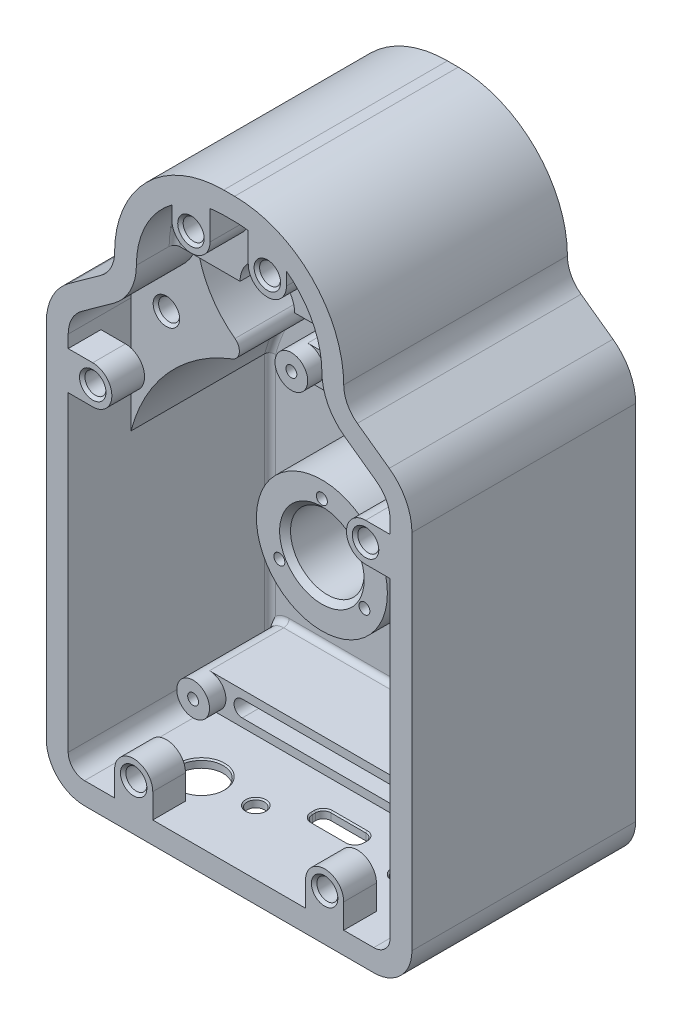
SolidWorks part; units mm, degrees
ref_plane "Plano frontal" through (0, 0, 0) normal (0, 0, 1) x (1, 0, 0)
ref_plane "Plano superior" through (0, 0, 0) normal (0, 1, 0) x (1, 0, 0)
ref_plane "Plano direito" through (0, 0, 0) normal (1, 0, 0) x (0, 0, -1)
sketch "Esboço1" plane through (0, 0, 0) normal (0, 0, 1) x (1, 0, 0)
  line L0 (-33.5, 0) -> (33.5, 0) construction
  line L1 (-33.5, -44.5) -> (33.5, -44.5)
  line L2 (-33.5, -44.5) -> (-33.5, 66)
  line L3 (-33.5, 66) -> (33.5, 66)
  line L4 (33.5, -44.5) -> (33.5, 66)
  point P0 (0, 0)
  point P8 (0, 0)
  dimension "D1" = 67
  dimension "D2" = 66
  dimension "D3" = 44.5
  dimension "D4" = 0
extrude "Ressalto-extrusão1" add sketch "Esboço1" along normal blind 4
sketch "Esboço2" plane through (0, 0, 4) normal (0, 0, 1) x (1, 0, 0)
  circle A0 centre (0, 0) radius 12
  dimension "D1" = 24
extrude "Ressalto-extrusão2" add sketch "Esboço2" along normal blind 20
sketch "Esboço3" plane through (0, 0, 24) normal (0, 0, 1) x (1, 0, 0)
  circle A0 centre (0, 9) radius 1
  circle A1 centre (7.7942, -4.5) radius 1
  circle A2 centre (-7.7942, -4.5) radius 1
  point P10 (0, 0)
  dimension "D1" = 9
  dimension "D2" = 2
  dimension "D3" = 3
extrude "Corte-extrusão1" cut sketch "Esboço3" against normal blind 6
sketch "Esboço4" plane through (0, 0, 4) normal (0, 0, 1) x (1, 0, 0)
  line L1 (5, -12.5) -> (-5, -12.5)
  line L2 (5, -12.5) -> (5, 12.5)
  line L3 (5, 12.5) -> (-5, 12.5)
  line L4 (-5, -12.5) -> (-5, 12.5)
  line L5 (5, -12.5) -> (-5, 12.5) construction
  line L6 (5, 12.5) -> (-5, -12.5) construction
  point P0 (0, 0)
  dimension "D1" = 10
  dimension "D2" = 25
extrude "Corte-extrusão2" cut sketch "Esboço4" along normal blind 8
sketch "Esboço5" plane through (0, 0, 24) normal (0, 0, 1) x (1, 0, 0)
  circle A0 centre (0, 0) radius 6.75
  dimension "D1" = 13.5
extrude "Corte-extrusão3" cut sketch "Esboço5" against normal up to surface (20 mm away) up to face at (-8.5, 0, 4)
sketch "Esboço6" plane through (0, 0, 4) normal (0, 0, 1) x (1, 0, 0)
  line L0 (0, 66) -> (0, -44.5) construction
  line L1 (33.5, 66) -> (-33.5, 66) construction
  line L2 (-33.5, -44.5) -> (33.5, -44.5) construction
  line L4 (26, -40) -> (-26, -40)
  line L6 (26, -34) -> (-26, -34)
  line L8 (-8, 27) -> (8, 27)
  line L9 (-8, 21) -> (8, 21)
  circle A0 centre (-26, -37) radius 1
  circle A1 centre (26, -37) radius 1
  arc A2 (-26, -34) -> (-26, -40) centre (-26, -37) ccw
  arc A3 (26, -34) -> (26, -40) centre (26, -37) cw
  circle A4 centre (-8, 24) radius 1
  arc A5 (-8, 27) -> (-8, 21) centre (-8, 24) ccw
  arc A6 (8, 27) -> (8, 21) centre (8, 24) cw
  circle A7 centre (8, 24) radius 1
  point P11 (0, -40)
  point P17 (0, -34)
  point P23 (0, 27)
  point P27 (0, 21)
  dimension "D1" = 26
  dimension "D2" = 37
  dimension "D3" = 2
  dimension "D5" = 2
  dimension "D7" = 24
  dimension "D8" = 8
  dimension "D9" = 6
  dimension "D4" = 3
  dimension "D6" = 3
extrude "Ressalto-extrusão3" add sketch "Esboço6" along normal blind 14.6
sketch "Esboço7" plane through (0, 0, 18.6) normal (0, 0, 1) x (1, 0, 0)
  line L0 (0, -34) -> (0, -40) construction
  line L1 (26, -34) -> (-26, -34) construction
  line L2 (-26, -40) -> (26, -40) construction
  circle A0 centre (-26, -37) radius 1
  circle A1 centre (-26, -37) radius 3
  circle A2 centre (26, -37) radius 3
  circle A3 centre (26, -37) radius 1
  circle A4 centre (-8, 24) radius 1
  circle A5 centre (-8, 24) radius 3
  circle A6 centre (8, 24) radius 1
  circle A7 centre (8, 24) radius 3
extrude "Ressalto-extrusão4" add sketch "Esboço7" along normal blind 3
sketch "Esboço12" plane through (0, 0, 4) normal (0, 0, 1) x (1, 0, 0)
  line L0 (0, 66) -> (0, -44.5) construction
  line L1 (-33.5, 66) -> (-21, 66)
  line L2 (-33.5, 66) -> (-33.5, 34)
  line L4 (-21, 66) -> (-21, 43)
  line L5 (33.5, 66) -> (-33.5, 66) construction
  line L6 (-33.5, -44.5) -> (33.5, -44.5) construction
  line L9 (33.5, 66) -> (33.5, 34)
  line L10 (33.5, 66) -> (21, 66)
  line L11 (-33.5, 34) -> (-21, 43)
  line L12 (33.5, 34) -> (21, 43)
  line L13 (21, 66) -> (21, 43)
  dimension "D1" = 32
  dimension "D2" = 23
  dimension "D3" = 12.5
extrude "Corte-extrusão4" cut sketch "Esboço12" against normal through all
sketch "Esboço10" plane through (0, 0, 4) normal (0, 0, 1) x (1, 0, 0)
  line L24 (-33.5, 34) -> (-21, 43)
  line L25 (-21, 43) -> (-21, 66)
  line L26 (-21, 66) -> (21, 66)
  line L27 (21, 66) -> (21, 43)
  line L28 (21, 43) -> (33.5, 34)
  line L29 (33.5, 34) -> (33.5, -44.5)
  line L30 (33.5, -44.5) -> (-33.5, -44.5)
  line L31 (-33.5, -44.5) -> (-33.5, 34)
  line L32 (-29.5, 31.9511) -> (-17, 40.9511)
  line L33 (-17, 40.9511) -> (-17, 62)
  line L34 (-17, 62) -> (17, 62)
  line L35 (17, 62) -> (17, 40.9511)
  line L36 (17, 40.9511) -> (29.5, 31.9511)
  line L37 (29.5, 31.9511) -> (29.5, -40.5)
  line L38 (29.5, -40.5) -> (-29.5, -40.5)
  line L39 (-29.5, -40.5) -> (-29.5, 31.9511)
  dimension "D1" = 4
extrude "Ressalto-extrusão5" add sketch "Esboço10" along normal blind 37
fillet "Filete5" radius 7 2 edges at (33.5, -44.5, 20.5) (-33.5, -44.5, 20.5)
fillet "Filete12" radius 3 2 edges at (29.5, -40.5, 22.5) (-29.5, -40.5, 22.5)
fillet "Filete13" radius 6 4 edges at (29.5, 31.9511, 22.5) (21, 43, 20.5) (-21, 43, 20.5) (-29.5, 31.9511, 22.5)
fillet "Filete14" radius 10 4 edges at (-33.5, 34, 20.5) (-17, 40.9511, 22.5) (33.5, 34, 20.5) (17, 40.9511, 22.5)
fillet "Filete15" radius 16 2 edges at (17, 62, 22.5) (-17, 62, 22.5)
fillet "Filete16" radius 20 2 edges at (21, 66, 20.5) (-21, 66, 20.5)
sketch "Esboço13" plane through (0, 0, 4) normal (0, 0, 1) x (1, 0, 0)
  line L0 (1.0001, 62) -> (-1.0001, 62) construction
  line L1 (-5, 46) -> (-17.0001, 46)
  line L2 (5, 46) -> (17.0001, 46)
  line L3 (-1.0001, 62) -> (1.0001, 62)
  arc A0 (-1.0001, 62) -> (-17.0001, 46) centre (-1.0001, 46) ccw
  arc A1 (17.0001, 46) -> (1.0001, 62) centre (1.0001, 46) ccw
  arc A2 (5, 46) -> (-5, 46) centre (0, 46) ccw
  dimension "D1" = 16
  dimension "D2" = 10
extrude "Ressalto-extrusão6" add sketch "Esboço13" along normal blind 4 from offset 26
sketch "Esboço14" plane through (0, 0, 34) normal (0, 0, 1) x (1, 0, 0)
  circle A0 centre (0, 58) radius 1.3
  circle A1 centre (10.3923, 52) radius 1.3
  circle A2 centre (10.3923, 40) radius 1.3
  circle A3 centre (0, 34) radius 1.3
  circle A4 centre (-10.3923, 40) radius 1.3
  circle A5 centre (-10.3923, 52) radius 1.3
  arc A6 (5, 46) -> (-5, 46) centre (0, 46) ccw construction
  point P15 (0, 46)
  dimension "D1" = 2.6
  dimension "D3" = 12
  dimension "D2" = 6
extrude "Corte-extrusão5" cut sketch "Esboço14" against normal blind 4
fillet "Filete17" radius 1 3 edges at (-12.2978, 57.3297, 34) (0, 62, 34) (12.2978, 57.3297, 34)
sketch "Esboço20" plane through (0, 0, 4) normal (0, 0, 1) x (1, 0, 0)
  line L4 (-29.5, 7.746) -> (-29.5, 28.8777)
  line L5 (-27.0058, 33.7469) -> (-21.157, 37.9581)
  arc A1 (-21.157, 37.9581) -> (-17.3262, 43.54) centre (-27, 46.0734) ccw
  arc A2 (-27.0058, 33.7469) -> (-29.5, 28.8777) centre (-23.5, 28.8777) ccw
  arc A3 (-6.5762, 29.7826) -> (-29.5, 7.746) centre (0, 0) ccw
  arc A4 (-17.3262, 43.54) -> (-6.5762, 29.7826) centre (0, 46) ccw
  dimension "D4" = 61
  dimension "D1" = 35
extrude "Ressalto-extrusão9" add sketch "Esboço20" along normal blind 25.5
fillet "Filete18" radius 2 1 edges at (-6.5762, 29.7826, 16.75)
sketch "Esboço21" plane through (0, 0, 29.5) normal (0, 0, 1) x (1, 0, 0)
  circle A0 centre (-23, 30) radius 1.925
  dimension "D1" = 30
  dimension "D2" = 23
  dimension "D3" = 3.85
extrude "Corte-extrusão6" cut sketch "Esboço21" against normal blind 6.5
sketch "Esboço22" plane through (0, 0, 4) normal (0, 0, 1) x (1, 0, 0)
  line L0 (0, 0) -> (0, -44.5) construction
  line L1 (-26.5, -44.5) -> (26.5, -44.5) construction
  line L2 (0, 0) -> (33.5, 0) construction
  line L3 (33.5, -37.5) -> (33.5, 28.8777) construction
  circle A0 centre (-18, -25) radius 4
  circle A1 centre (18, -25) radius 4
  circle A2 centre (18, 25) radius 4
  circle A3 centre (-18, 25) radius 4
  circle A4 centre (0, 53) radius 4
  arc A5 (5, 46) -> (-5, 46) centre (0, 46) ccw construction
  dimension "D1" = 8
  dimension "D2" = 18
  dimension "D3" = 25
  dimension "D4" = 8
  dimension "D5" = 7
extrude "Ressalto-extrusão10" add sketch "Esboço22" along normal blind 2
sketch "Esboço23" plane through (0, 0, 6) normal (0, 0, 1) x (1, 0, 0)
  circle A0 centre (0, 53) radius 1.925
  circle A1 centre (-18, 25) radius 1.925
  circle A2 centre (18, 25) radius 1.925
  circle A3 centre (-18, -25) radius 1.925
  circle A4 centre (18, -25) radius 1.925
  dimension "D1" = 3.85
  dimension "D2" = 3.85
  dimension "D3" = 3.85
  dimension "D4" = 3.85
  dimension "D5" = 3.85
extrude "Corte-extrusão7" cut sketch "Esboço23" against normal through all from offset 1.5 offset against normal yes
sketch "Esboço24" plane through (0, 0, 41) normal (0, 0, 1) x (1, 0, 0)
  line L0 (-10.5, 56.5) -> (-10.5, 58.8745)
  line L1 (-3.5, 56.5) -> (-3.5, 61.8035)
  line L2 (0, 46) -> (0, 62) construction
  line L3 (1.0001, 62) -> (-1.0001, 62) construction
  line L4 (3.5, 56.5) -> (3.5, 61.8035)
  line L5 (10.5, 56.5) -> (10.5, 58.8745)
  arc A2 (-10.5, 56.5) -> (-3.5, 56.5) centre (-7, 56.5) ccw
  arc A3 (5, 46) -> (-5, 46) centre (0, 46) ccw construction
  arc A4 (-3.5, 61.8035) -> (-10.5, 58.8745) centre (-1.0001, 46) ccw
  arc A5 (3.5, 61.8035) -> (10.5, 58.8745) centre (1.0001, 46) cw
  arc A6 (10.5, 56.5) -> (3.5, 56.5) centre (7, 56.5) cw
  dimension "D2" = 7
  dimension "D3" = 10.5
extrude "Ressalto-extrusão11" add sketch "Esboço24" against normal up to surface (7 mm away) up to face at (1.3, 58, 34)
sketch "Esboço25" plane through (0, 0, 41) normal (0, 0, 1) x (1, 0, 0)
  line L0 (0, 0) -> (0, 66) construction
  line L1 (1.0001, 66) -> (-1.0001, 66) construction
  line L2 (-25, 26.5788) -> (-29.5, 26.5788)
  line L3 (-29.5, 28.8777) -> (-29.5, -37.5) construction
  line L4 (-29.5, 26.5788) -> (-29.5, 19.5788)
  line L5 (-29.5, 19.5788) -> (-25, 19.5788)
  line L6 (29.5, 19.5788) -> (25, 19.5788)
  line L7 (29.5, 26.5788) -> (29.5, 19.5788)
  line L8 (25, 26.5788) -> (29.5, 26.5788)
  line L9 (-26.5, -40.5) -> (26.5, -40.5) construction
  line L10 (-21, -36) -> (-21, -40.5)
  line L11 (-21, -40.5) -> (-14, -40.5)
  line L12 (-14, -40.5) -> (-14, -36)
  line L13 (-29.5, 7.746) -> (-29.5, -37.5) construction
  line L14 (14, -40.5) -> (14, -36)
  line L15 (21, -40.5) -> (14, -40.5)
  line L16 (21, -36) -> (21, -40.5)
  arc A0 (-25, 19.5788) -> (-25, 26.5788) centre (-25, 23.0788) ccw
  arc A1 (25, 19.5788) -> (25, 26.5788) centre (25, 23.0788) cw
  arc A2 (-14, -36) -> (-21, -36) centre (-17.5, -36) ccw
  arc A3 (14, -36) -> (21, -36) centre (17.5, -36) cw
  dimension "D1" = 7
  dimension "D2" = 4.5
  dimension "D3" = 7
  dimension "D4" = 4.5
  dimension "D5" = 12
extrude "Ressalto-extrusão12" add sketch "Esboço25" against normal blind 6
sketch "Esboço27" plane through (0, 0, 41) normal (0, 0, 1) x (1, 0, 0)
  line L0 (0, 0) -> (0, 21) construction
  line L1 (-8, 21) -> (8, 21) construction
  circle A0 centre (-7, 56.5) radius 1.925
  circle A1 centre (-25, 23.0788) radius 1.925
  circle A2 centre (-17.5, -36) radius 1.925
  circle A3 centre (17.5, -36) radius 1.925
  circle A4 centre (25, 23.0788) radius 1.925
  circle A5 centre (7, 56.5) radius 1.925
  dimension "D1" = 3.85
  dimension "D2" = 3.85
  dimension "D3" = 3.85
extrude "Corte-extrusão8" cut sketch "Esboço27" against normal blind 5
sketch "Esboço28" plane through (0, -44.5, 0) normal (0, -1, 0) x (1, 0, 0)
  line L0 (-26.5, 0) -> (26.5, 0) construction
  line L1 (-33.5, 0) -> (-33.5, 41) construction
  line L3 (0.93, 23.28) -> (7.33, 23.28)
  line L4 (-0.47, 24.68) -> (-0.47, 25.28)
  line L5 (0.93, 26.68) -> (7.33, 26.68)
  line L6 (8.73, 24.68) -> (8.73, 25.28)
  line L7 (-0.47, 23.28) -> (8.73, 26.68) construction
  line L8 (-0.47, 26.68) -> (8.73, 23.28) construction
  circle A0 centre (-16.43, 29.65) radius 4
  circle A1 centre (-6.86, 29.25) radius 1.6
  arc A2 (7.33, 23.28) -> (8.73, 24.68) centre (7.33, 24.68) ccw
  arc A3 (7.33, 26.68) -> (8.73, 25.28) centre (7.33, 25.28) cw
  arc A4 (0.93, 23.28) -> (-0.47, 24.68) centre (0.93, 24.68) cw
  arc A5 (-0.47, 25.28) -> (0.93, 26.68) centre (0.93, 25.28) cw
  circle A6 centre (17.49, 26.75) radius 1.7
  point P8 (4.13, 24.98)
  dimension "D1" = 29.65
  dimension "D2" = 17.07
  dimension "D3" = 8
  dimension "D4" = 9.57
  dimension "D5" = 0.4
  dimension "D6" = 3.2
  dimension "D11" = 1.4
  dimension "D12" = 1.77
  dimension "D13" = 13.36
  dimension "D14" = 3.4
  dimension "D7" = 4.27
  dimension "D8" = 10.99
  dimension "D9" = 9.2
  dimension "D10" = 3.4
extrude "Corte-extrusão9" cut sketch "Esboço28" against normal up to surface (4 mm away) up to face at (0, -40.5, 32.8333)
sketch "Esboço29" plane through (0, -44.5, 0) normal (0, -1, 0) x (1, 0, 0)
  line L0 (-24.43, 37.65) -> (23.19, 37.65)
  line L1 (-20.43, 33.65) -> (19.19, 33.65) construction
  line L2 (-20.43, 33.65) -> (-20.43, 23.28) construction
  line L3 (-20.43, 23.28) -> (19.19, 23.28) construction
  line L4 (19.19, 33.65) -> (19.19, 23.28) construction
  line L5 (23.19, 37.65) -> (23.19, 19.28)
  line L6 (-24.43, 19.28) -> (23.19, 19.28)
  line L7 (-24.43, 37.65) -> (-24.43, 19.28)
  circle A0 centre (-16.43, 29.65) radius 4 construction
  circle A1 centre (17.49, 26.75) radius 1.7 construction
  dimension "D2" = 4
  dimension "D3" = 4
  dimension "D4" = 1.7
  dimension "D5" = 10.37
  dimension "D1" = 4
extrude "Corte-extrusão10" cut sketch "Esboço29" against normal blind 2.5
chamfer "Chanfro1" distance 2.5 angle 45 4 edges at (-0.62, -42, 19.28) (-24.43, -42, 28.465) (-0.62, -42, 37.65) (23.19, -42, 28.465)
chamfer "Chanfro2" distance 1 angle 45 1 edges at (6.75, 0, 24)
fillet "Filete21" radius 1 37 edges at (0, 21, 4) (11, 24, 4) (0, 27, 4) (-11, 24, 4) (0, -40, 4) (29, -37, 4) (0, -34, 4) (-29, -37, 4) (5, -7.7217, 4) (12, 0, 4) (5, 7.7217, 4) (6.75, 0, 4) (-12, 0, 4) (-5, -7.7217, 4) (-6.75, 0, 4) (-5, 7.7217, 4) (-22, -25, 4) (14, -25, 4) (14, 25, 4) (-12.7115, 27.7248, 4) (-9.6487, 30.0756, 4) (-15.0422, 37.0567, 4) (-17.0837, 44.7822, 4) (-12.2978, 57.3297, 4) (0, 62, 4) (12.2978, 57.3297, 4) (18.1062, 41.5018, 4) (24.0814, 35.8525, 4) (28.8402, 31.6131, 4) (29.5, -4.3112, 4) (28.6213, -39.6213, 4) (0, -40.5, 4) (-28.6213, -39.6213, 4) (-29.5, -14.877, 4) (-26.2121, 15.594, 4) (-15.6628, 21.7539, 4) (-4, 53, 4)
chamfer "Chanfro3" distance 0.5 angle 45 5 edges at (14, -25, 6) (-14, -25, 6) (22, 25, 6) (4, 53, 6) (-15.6628, 21.7539, 6)
chamfer "Chanfro4" distance 0.5 angle 45 5 edges at (19.925, -25, 0) (-16.075, -25, 0) (1.925, 53, 0) (-16.075, 25, 0) (19.925, 25, 0)
chamfer "Chanfro5" distance 0.25 angle 45 11 edges at (-16.43, -40.5, 33.65) (-6.86, -40.5, 30.85) (4.13, -40.5, 26.68) (-0.0599, -40.5, 26.2699) (8.3199, -40.5, 26.2699) (-0.47, -40.5, 24.98) (8.73, -40.5, 24.98) (-0.0599, -40.5, 23.6901) (8.3199, -40.5, 23.6901) (4.13, -40.5, 23.28) (17.49, -40.5, 28.45)
sketch "Esboço31" plane through (0, 0, 18.6) normal (0, 0, 1) x (1, 0, 0)
  line L0 (-20, -35.5) -> (20, -35.5)
  line L1 (-20, -38.5) -> (20, -38.5)
  line L2 (-2, 25.5) -> (2, 25.5)
  line L3 (-2, 22.5) -> (2, 22.5)
  arc A0 (-20, -35.5) -> (-20, -38.5) centre (-20, -37) ccw
  arc A1 (-26, -40) -> (-26, -34) centre (-26, -37) ccw construction
  arc A2 (20, -38.5) -> (20, -35.5) centre (20, -37) ccw
  circle A3 centre (26, -37) radius 3 construction
  arc A4 (-2, 25.5) -> (-2, 22.5) centre (-2, 24) ccw
  arc A5 (2, 22.5) -> (2, 25.5) centre (2, 24) ccw
  arc A6 (8, 27) -> (8, 21) centre (8, 24) ccw construction
  circle A7 centre (-8, 24) radius 3 construction
  dimension "D1" = 3
  dimension "D2" = 6
  dimension "D3" = 3
  dimension "D4" = 6
  dimension "D5" = 3
  dimension "D6" = 3
  dimension "D7" = 6
  dimension "D8" = 6
extrude "Corte-extrusão11" cut sketch "Esboço31" against normal blind 14
chamfer "Chanfro6" distance 0.5 angle 45 6 edges at (-15.575, -36, 41) (15.575, -36, 41) (23.075, 23.0788, 41) (-23.075, 23.0788, 41) (5.075, 56.5, 41) (-5.075, 56.5, 41)
chamfer "Chanfro7" distance 0.5 angle 45 1 edges at (-21.075, 30, 29.5)
